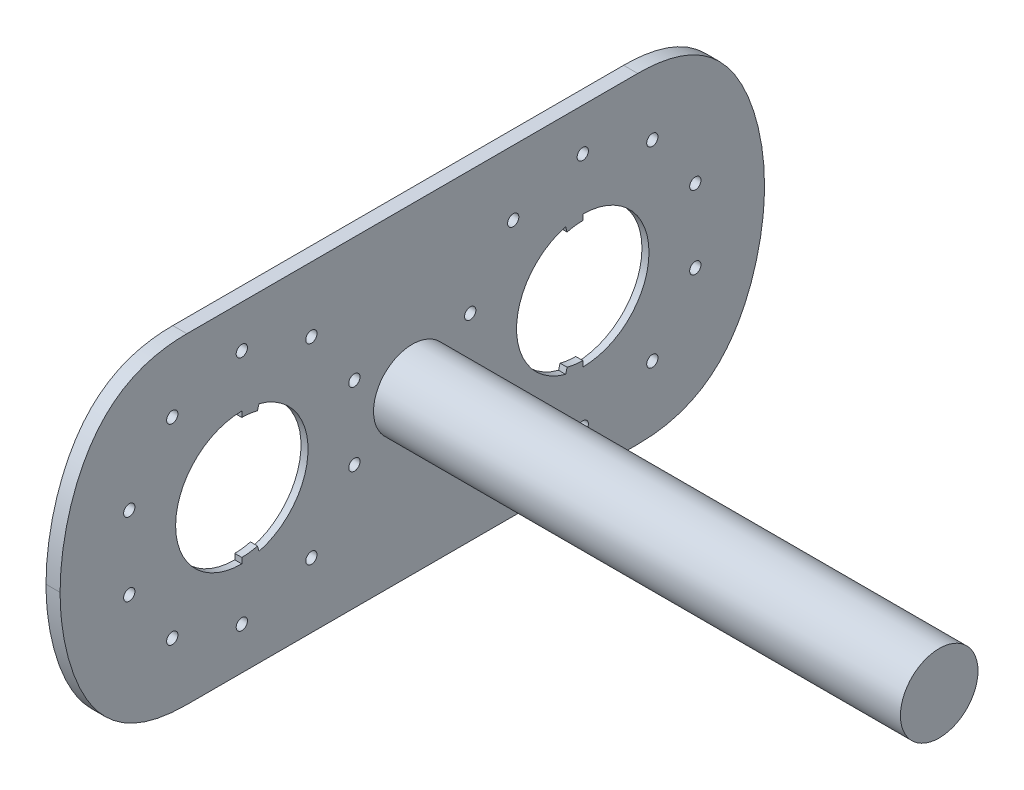
SolidWorks part; units mm, degrees
ref_plane "前视基准面" through (0, 0, 0) normal (0, 0, 1) x (1, 0, 0)
ref_plane "上视基准面" through (0, 0, 0) normal (0, 1, 0) x (1, 0, 0)
ref_plane "右视基准面" through (0, 0, 0) normal (1, 0, 0) x (0, 0, -1)
sketch "草图1" plane through (0, 0, 0) normal (1, 0, 0) x (0, 0, -1)
  line L0 (0, 57) -> (80, 57)
  line L1 (80, -57) -> (0, -57)
  line L2 (0, 57) -> (0, -57)
  line L3 (80, 57) -> (110.7152, 57) construction
  line L4 (110.7152, 57) -> (118.0231, 36.993) construction
  line L5 (118.0231, 36.993) -> (125, 20.498) construction
  line L6 (125, 20.498) -> (125, 0) construction
  line L7 (0, 0) -> (125, 0) construction
  line L8 (80, -57) -> (110.7152, -57) construction
  line L9 (110.7152, -57) -> (118.0231, -36.993) construction
  line L10 (118.0231, -36.993) -> (125, -20.498) construction
  line L11 (125, -20.498) -> (125, 0) construction
  circle A0 centre (60.5, 0) radius 48 construction
  spline S0 degree 4 poles (80, 57) (110.7152, 57) (118.0231, 36.993) (125, 20.498) (125, 0) knots 0 0 0 0 0 1 1 1 1 1
  spline S1 degree 4 poles (80, -57) (110.7152, -57) (118.0231, -36.993) (125, -20.498) (125, 0) knots 0 0 0 0 0 1 1 1 1 1
  dimension "D1" = 60.5
  dimension "D2" = 96
  dimension "D4" = 125
  dimension "D3" = 57
  dimension "D6" = 80
extrude "凸台-拉伸1" add sketch "草图1" along normal blind 5
sketch "草图2" plane through (0, 0, 0) normal (-1, 0, 0) x (0, 0, 1)
  circle A0 centre (-60.5, 0) radius 31
  dimension "D1" = 60.5
  dimension "D2" = 62
extrude "切除-拉伸1" cut sketch "草图2" against normal blind 2.5
sketch "草图3" plane through (0, 0, 0) normal (-1, 0, 0) x (0, 0, 1)
  line L0 (-60.5, 0) -> (-60.5, 79.1647) construction
  line L1 (-60.5, 0) -> (-60.5, 42) construction
  circle A1 centre (-60.5, 42) radius 2
  dimension "D1" = 0
  dimension "D2" = 42
  dimension "D3" = 4
extrude "切除-拉伸2" cut sketch "草图3" against normal up to next
pattern_circular "阵列(圆周)1" count 10 over 360 about axis through (0, 0, -60.5) along (-1, 0, 0) of "切除-拉伸2"
sketch "草图4" plane through (2.5, 0, 0) normal (-1, 0, 0) x (0, 0, 1)
  circle A0 centre (-60.5, 0) radius 23.5
  dimension "D1" = 47
extrude "切除-拉伸3" cut sketch "草图4" against normal up to next
sketch "草图5" plane through (5, 0, 0) normal (1, 0, 0) x (0, 0, -1)
  circle A0 centre (60.5, 0) radius 34.5
  circle A1 centre (60.5, 0) radius 37.5
  dimension "D1" = 75
  dimension "D2" = 69
sketch "草图7" plane through (0, 0, 0) normal (-1, 0, 0) x (0, 0, 1)
  line L0 (-60.5, 48) -> (-81.7662, 48)
  line L1 (-60.5, -48) -> (-81.7662, -48)
  arc A0 (-60.5, 48) -> (-60.5, -48) centre (-60.5, 0) ccw
  arc A1 (-81.7662, 48) -> (-81.7662, -48) centre (-60.5, 0) ccw
  dimension "D1" = 96
  dimension "D2" = 105
sketch "草图8" plane through (5, 0, 0) normal (1, 0, 0) x (0, 0, -1)
  line L0 (54.9354, 20.7674) -> (54.4178, 22.6993)
  line L1 (60.5, 21.5) -> (60.5, 23.5)
  line L2 (60.5, 0) -> (0, 0) construction
  line L3 (60.5, -21.5) -> (60.5, -23.5)
  line L4 (54.9354, -20.7674) -> (54.4178, -22.6993)
  circle A0 centre (60.5, 0) radius 23.5 construction
  arc A1 (60.5, 23.5) -> (54.4178, 22.6993) centre (60.5, 0) ccw
  arc A2 (60.5, 21.5) -> (54.9354, 20.7674) centre (60.5, 0) ccw
  arc A3 (60.5, -21.5) -> (54.9354, -20.7674) centre (60.5, 0) cw
  arc A4 (60.5, -23.5) -> (54.4178, -22.6993) centre (60.5, 0) cw
  dimension "D1" = 43
  dimension "D2" = 15
extrude "凸台-拉伸3" add sketch "草图8" against normal up to surface (2.5 mm away) up to face at (2.5, 0, -37)
mirror "镜向3" about plane through (5, 57, 0) normal (0, 0, -1) of bodies 122 114
sketch "草图9" plane through (5, 0, 0) normal (1, 0, 0) x (0, 0, -1)
  circle A0 centre (0, 0) radius 13.7633
extrude "凸台-拉伸4" add sketch "草图9" along normal blind 187
